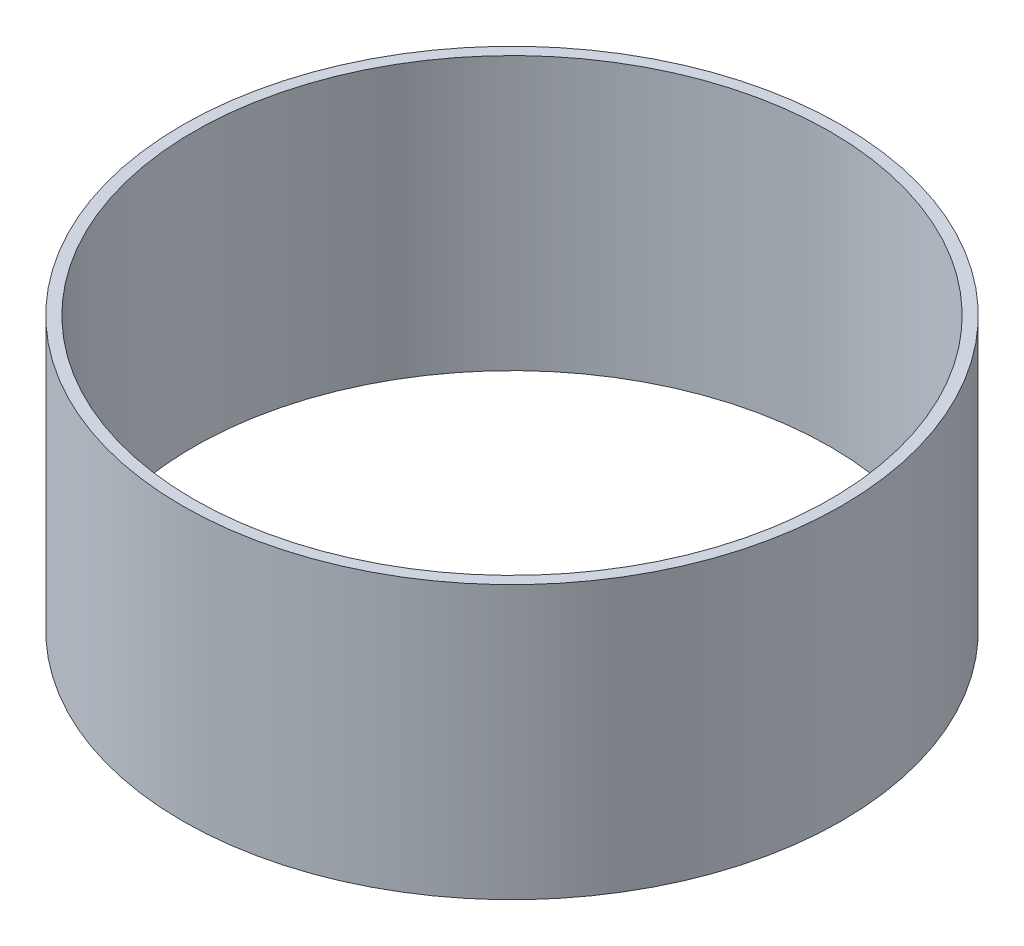
SolidWorks part; units mm, degrees
material "Acrylic (Medium-high impact)"
ref_plane "Front Plane" through (0, 0, 0) normal (0, 0, 1) x (1, 0, 0)
ref_plane "Top Plane" through (0, 0, 0) normal (0, 1, 0) x (1, 0, 0)
ref_plane "Right Plane" through (0, 0, 0) normal (1, 0, 0) x (0, 0, -1)
sketch "Sketch1" plane through (0, 0, 0) normal (0, 1, 0) x (1, 0, 0)
  circle A0 centre (0, 0) radius 92.075
  circle A1 centre (0, 0) radius 88.9
  dimension "D1" = 184.15
  dimension "D2" = 177.8
extrude "Boss-Extrude1" add sketch "Sketch1" along normal mid plane 76.2
ref_plane "Plane1" through (92.075, 0, 0) normal (1, 0, 0) x (0, 0, -1)
sketch "Sketch3" plane through (92.075, 0, 0) normal (1, 0, 0) x (0, 0, -1)
  line L0 (0, 103.0288) -> (0, -103.0288) construction
  line L1 (88.9, 38.1) -> (-88.9, 38.1) construction
  line L2 (-92.075, -38.1) -> (92.075, -38.1) construction
  circle A0 centre (0, -31.75) radius 1.4351
  circle A1 centre (0, 31.75) radius 1.4351
  dimension "D1" = 6.35
  dimension "D2" = 2.8702
  dimension "D3" = 2.8702
  dimension "D4" = 6.35
extrude "Cut-Extrude1" [suppressed] cut sketch "Sketch3" against normal blind 34.798
pattern_circular "CirPattern1" [suppressed] count 3 over 360 of bodies 102
